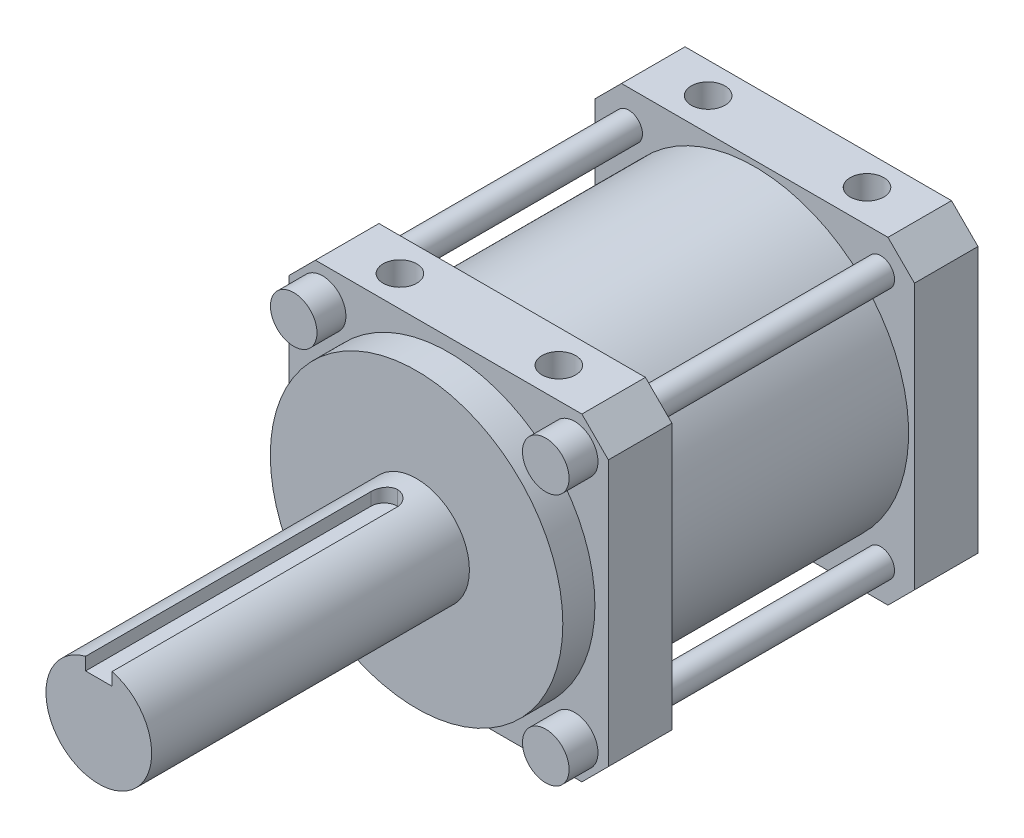
SolidWorks part; units mm, degrees
ref_plane "Front Plane" through (0, 0, 0) normal (0, 0, 1) x (1, 0, 0)
ref_plane "Top Plane" through (0, 0, 0) normal (0, 1, 0) x (1, 0, 0)
ref_plane "Right Plane" through (0, 0, 0) normal (1, 0, 0) x (0, 0, -1)
sketch "Sketch1" plane through (0, 0, 0) normal (0, 0, 1) x (1, 0, 0)
  circle A0 centre (0, 0) radius 18.4531
  dimension "D1" = 36.9062
extrude "Can" add sketch "Sketch1" along normal mid plane 29.083
sketch "Sketch2" plane through (0, 0, 14.5415) normal (0, 0, 1) x (1, 0, 0)
  line L1 (-19.1516, -19.1008) -> (19.1516, -19.1008)
  line L2 (-19.1516, -19.1008) -> (-19.1516, 19.1008)
  line L3 (-19.1516, 19.1008) -> (19.1516, 19.1008)
  line L4 (19.1516, -19.1008) -> (19.1516, 19.1008)
  line L5 (-19.1516, -19.1008) -> (19.1516, 19.1008) construction
  line L6 (-19.1516, 19.1008) -> (19.1516, -19.1008) construction
  point P0 (0, 0)
  dimension "D1" = 38.3032
  dimension "D2" = 38.2016
extrude "Front Flange" add sketch "Sketch2" along normal blind 7.62
sketch "Sketch3" plane through (0, 0, 22.1615) normal (0, 0, 1) x (1, 0, 0)
  circle A0 centre (0, 0) radius 17.5387
  dimension "D1" = 35.0774
extrude "Front Bearing" add sketch "Sketch3" along normal blind 3.8481
sketch "Sketch4" plane through (0, 0, 26.0096) normal (0, 0, 1) x (1, 0, 0)
  circle A0 centre (0, 0) radius 6.3373
  dimension "D1" = 12.6746
extrude "Shaft" add sketch "Sketch4" along normal blind 38.1
sketch "Sketch6" plane through (0, 0, 64.1096) normal (0, 0, 1) x (1, 0, 0)
  line L0 (-1.5875, 6.1352) -> (-1.5875, 4.6112)
  line L1 (-1.5875, 4.6112) -> (1.5875, 4.6112)
  line L2 (1.5875, 4.6112) -> (1.5875, 6.1352)
  line L3 (0, 0) -> (0, 4.6112) construction
  circle A0 centre (0, 0) radius 6.3373 construction
  circle A1 centre (0, 0) radius 6.3373 construction
  circle A2 centre (0, 0) radius 6.3373
  circle A3 centre (0, 0) radius 6.3373 construction
  arc A4 (-1.5875, 6.1352) -> (1.5875, 6.1352) centre (0, 0) cw
  dimension "D2" = 3.175
  dimension "D3" = 1.524
  dimension "D1" = 0
extrude "Keyway" cut sketch "Sketch6" against normal offset from surface (35.814 mm away) 2.286 up to face at (6.3373, 0, 26.0096)
mirror "Back Flange" about plane through (0, 0, 0) normal (0, 0, 1) of "Front Flange"
sketch "Sketch7" plane through (0, 0, 22.1615) normal (0, 0, 1) x (1, 0, 0)
  line L1 (-17.907, -17.907) -> (17.907, -17.907) construction
  line L2 (-17.907, -17.907) -> (-17.907, 17.907) construction
  line L3 (-17.907, 17.907) -> (17.907, 17.907) construction
  line L4 (17.907, -17.907) -> (17.907, 17.907) construction
  line L5 (-17.907, -17.907) -> (17.907, 17.907) construction
  line L6 (-17.907, 17.907) -> (17.907, -17.907) construction
  circle A0 centre (15.113, 15.113) radius 2.794
  circle A1 centre (-15.113, 15.113) radius 2.794
  circle A2 centre (-15.113, -15.113) radius 2.794
  circle A3 centre (15.113, -15.113) radius 2.794
  point P0 (0, 0)
  dimension "D1" = 5.588
  dimension "D2" = 35.814
extrude "Screw Heads" add sketch "Sketch7" along normal blind 3.4671
sketch "Sketch8" plane through (0, 0, 22.1615) normal (0, 0, 1) x (1, 0, 0)
  circle A0 centre (-15.113, 15.113) radius 1.651
  circle A1 centre (15.113, 15.113) radius 1.651
  circle A2 centre (15.113, -15.113) radius 1.651
  circle A3 centre (-15.113, -15.113) radius 1.651
  dimension "D1" = 3.302
extrude "Screw Threads" add sketch "Sketch8" against normal up to surface (36.703 mm away) up to face at (18.4531, 0, -14.5415)
sketch "Hole Pattern Measurements" plane through (0, 19.1008, 0) normal (0, 1, 0) x (1, 0, 0)
  line L0 (-7.366, 16.3195) -> (-7.366, 22.1615) construction
  line L1 (-7.366, -16.3195) -> (7.366, -16.3195)
  line L2 (-7.366, -16.3195) -> (-7.366, 16.3195)
  line L3 (-7.366, 16.3195) -> (7.366, 16.3195)
  line L4 (7.366, -16.3195) -> (7.366, 16.3195)
  line L5 (-7.366, -16.3195) -> (7.366, 16.3195) construction
  line L6 (-7.366, 16.3195) -> (7.366, -16.3195) construction
  line L7 (-7.366, 16.3195) -> (-19.3255, 16.3195) construction
  line L9 (19.1516, 22.1615) -> (-19.1516, 22.1615) construction
  line L10 (7.366, 16.3195) -> (19.3255, 16.3195) construction
  line L12 (7.366, 16.3195) -> (7.366, 22.1615) construction
  line L13 (-7.366, -16.3195) -> (-7.366, -22.1615) construction
  line L14 (19.1516, -22.1615) -> (-19.1516, -22.1615) construction
  line L15 (-7.366, -16.3195) -> (-19.3255, -16.3195) construction
  line L17 (7.366, -16.3195) -> (19.3255, -16.3195) construction
  line L19 (7.366, -16.3195) -> (7.366, -22.1615) construction
  circle A0 centre (-9.525, 18.4785) radius 2.159
  circle A1 centre (9.525, 18.4785) radius 2.159
  circle A2 centre (-9.525, -18.4785) radius 2.159
  circle A3 centre (9.525, -18.4785) radius 2.159
  point P0 (0, 0)
  dimension "D1" = 4.318
  dimension "D2" = 14.732
  dimension "D3" = 32.639
hole_wizard "#10-32 Tapped Hole1" positions "Sketch11" profile "Sketch10" tap size "#10-32" standard "ANSI Inch"
sketch "Sketch11" plane through (0, 19.1008, 0) normal (0, 1, 0) x (1, 0, 0)
  point P0 (-9.525, -18.4785)
  point P3 (9.525, -18.4785)
  point P6 (9.525, 18.4785)
  point P9 (-9.525, 18.4785)
sketch "Sketch10" plane through (-9.525, 19.1008, 18.4785) normal (1, 0, 0) x (0, 0, 1)
  line L0 (0, 0) -> (0, 7.5633)
  line L1 (0, 7.5633) -> (2.0193, 6.35)
  line L2 (2.0193, 6.35) -> (2.0193, 0)
  line L5 (2.0193, 0) -> (0, 0)
  line L10 (0, 7.5633) -> (-2.0193, 6.35) construction
  line L11 (0, -6.35) -> (0, 107.95) construction
  dimension "Tap Drill Dia." = 4.0386
  dimension "Tap Drill Depth" = 6.35
  dimension "Drill Angle" = 118
mirror "#10-32 Tapped Hole2" about plane through (0, 0, 0) normal (0, 1, 0) of "#10-32 Tapped Hole1"
sketch "Sketch12" plane through (0, 0, -22.1615) normal (0, 0, -1) x (-1, 0, 0)
  circle A0 centre (0, 0) radius 8.763
  dimension "D1" = 17.526
extrude "Back Recess" cut sketch "Sketch12" against normal blind 6.35
sketch "Sketch13" plane through (0, 0, -15.8115) normal (0, 0, -1) x (-1, 0, 0)
  circle A0 centre (0, 0) radius 3.175
  dimension "D1" = 6.35
extrude "Pinion Recess" cut sketch "Sketch13" against normal offset from surface (9.398 mm away) 15.748 up to face at (-8.763, 0, -22.1615)
chamfer "Flange Chamfers" distance 3.175 8 edges at (-19.1516, 19.1008, 18.3515) (-19.1516, 19.1008, -18.3515) (-19.1516, -19.1008, 18.3515) (-19.1516, -19.1008, -18.3515) (19.1516, -19.1008, -18.3515) (19.1516, 19.1008, -18.3515) (19.1516, 19.1008, 18.3515) (19.1516, -19.1008, 18.3515)
fillet "Keyway Fillet" radius 1.5875 2 edges at (-1.5875, 5.3732, 28.2956) (1.5875, 5.3732, 28.2956)
